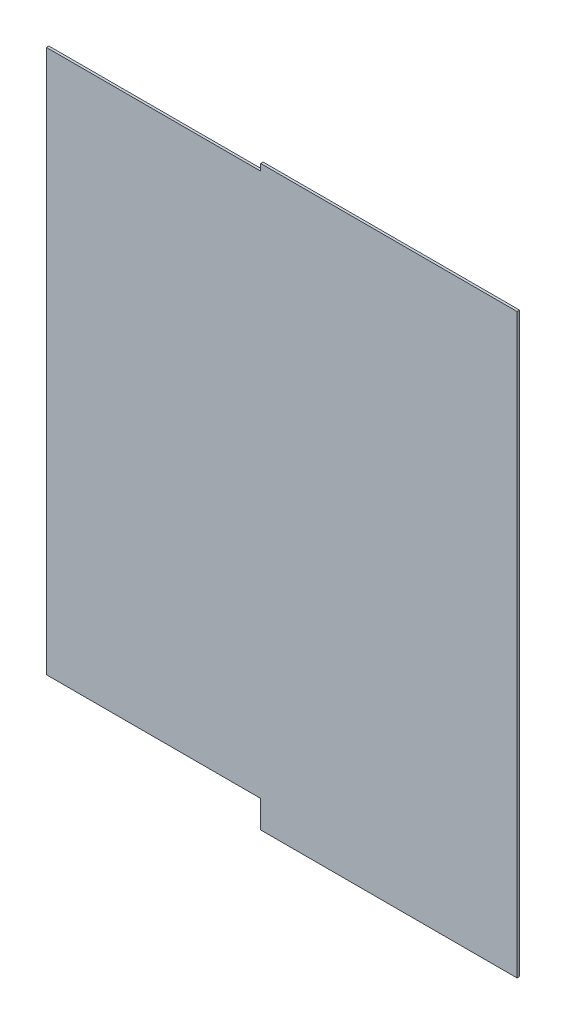
SolidWorks part; units mm, degrees
ref_plane "Спереди" through (0, 0, 0) normal (0, 0, 1) x (1, 0, 0)
ref_plane "Сверху" through (0, 0, 0) normal (0, 1, 0) x (1, 0, 0)
ref_plane "Справа" through (0, 0, 0) normal (1, 0, 0) x (0, 0, -1)
sketch "Эскиз1" plane through (0, 0, 0) normal (0, 0, 1) x (1, 0, 0)
  line L0 (0, -883) -> (518, -883)
  line L1 (1138.3, -949) -> (518, -949)
  line L2 (0, -883) -> (0, 431)
  line L3 (0, 431) -> (518, 431)
  line L4 (518, 431) -> (518, 447)
  line L5 (518, 447) -> (1138.3, 447)
  line L6 (1138.3, 447) -> (518, 447) construction
  line L7 (1138.3, 441) -> (1138.3, 447) construction
  line L8 (1138.3, 447) -> (1138.3, -949)
  line L9 (518, 447) -> (518, -949) construction
  line L10 (0, -883) -> (524, -883) construction
  line L11 (518, -883) -> (518, -949)
  point P0 (0, -883)
extrude "Бобышка-Вытянуть1" add sketch "Эскиз1" against normal blind 6
equation "\"Ширина груза\"= 420"
equation "\"Глубина груза\"= 490"
equation "\"Высота груза\"= 297"
equation "\"Ширина ячейки\"= \"Ширина груза\" + 10"
equation "\"Глубина ячейки\"= \"Глубина груза\" + 10"
equation "\"Высота ячейки\"= \"Высота груза\" + 10 + 13"
equation "\"Колво ячеек ширина\"= 2"
equation "\"Колво ячеек высота\"= 2"
equation "\"Толщина стенки\" = 6"
equation "\"Крепление дверцы\"= 5 "
equation "\"Ширина рейки\"= \"Толщина шестерни\""
equation "\"Высота рейки\"= 20"
equation "\"Высота пола\"= \"Толщина стенки\" * 2"
equation "\"Колво полозьев\"= 5"
equation "\"Отступ рейки\"= 20"
equation "\"Глубина каретки\"= \"Глубина ячейки\" + 30 + \"Мотор Y высота корпуса\" + 20"
equation "\"Длинна рейки\"= ( \"Ширина ячейки\" + \"Толщина стенки\" + \"Крепление дверцы\" ) * \"Колво ячеек ширина\" + \"Ширина ячейки выгрузки\" * \"Колво выгрузки\" + \"Толщина стенки\""
equation "\"Отступ шпильки\"= 26"
equation "\"Диаметр шпильки\"= 5"
equation "\"Длинна шпильки\"= ( \"Высота ячейки\" + \"Толщина стенки\" + \"Высота пола\" ) * \"Колво ячеек высота\" + ( \"Толщина стенки\" + \"Отступ рейки\" ) * 2 "
equation "\"Ширина пластины\"= 50  "
equation "\"Высота зона выгрузки\"= \"Высота ячейки\" * 2 + \"Толщина стенки\" * 2"
equation "\"Колво выгрузки\"= 1"
equation "\"Ширина ячейки выгрузки\"= \"Ширина ячейки\" + \"Толщина стенки\" + \"Отступ крепления мотора фиксации\"*2"
equation "\"Отступ крепления мотора фиксации\" = 30"
equation "\"Мотор X ширина корпуса\"= 42.3"
equation "\"Мотор X высота корпуса\"= 42.3"
equation "\"Мотор X длина корпуса\"= 40"
equation "\"Мотор X вылет вала\"= 19.8"
equation "\"Мотор Y ширина корпуса\"= 42.3"
equation "\"Мотор Y высота корпуса\"= 42.3"
equation "\"Мотор Y длина корпуса\"= 48"
equation "\"Мотор Y вылет вала\"= 30"
equation "\"Мотор Z ширина корпуса\"= 42"
equation "\"Мотор Z высота корпуса\"= 42"
equation "\"Мотор Z длина корпуса\"= 40"
equation "\"Мотор Z вылет вала\"= 23"
equation "\"Мотор диаметр вала ПРЕДВ\"= 5"
equation "\"Мотор шаг крепления ПРЕДВ\"= 31"
equation "\"Мотор диаметр отверстий ПРЕДВ\"= 3"
equation "\"Мотор глубина отверстий ПРЕДВ\"= 4.5"
equation "\"Мотор диаметр буртика ПРЕДВ\"= 22"
equation "\"Мотор высота буртика ПРЕДВ\"= 2"
equation "\"Мотор диаметр шкива ПРЕДВ\"= 16"
equation "\"Мотор длина шкива ПРЕДВ\"= 12"
equation "\"Мотор отступ шкива ПРЕДВ\"= 5"
equation "\"Мотор X шаг градусов\"= 1.8"
equation "\"Мотор Y шаг градусов\"= 1.8"
equation "\"Мотор Z шаг градусов\"= 1.8"
equation "\"Мотор Y диаметр ротора\"= 25.78"
equation "\"Толщина шестерни\"= 10"
equation "\"D1@Бобышка-Вытянуть1\"=\"Толщина стенки\""
